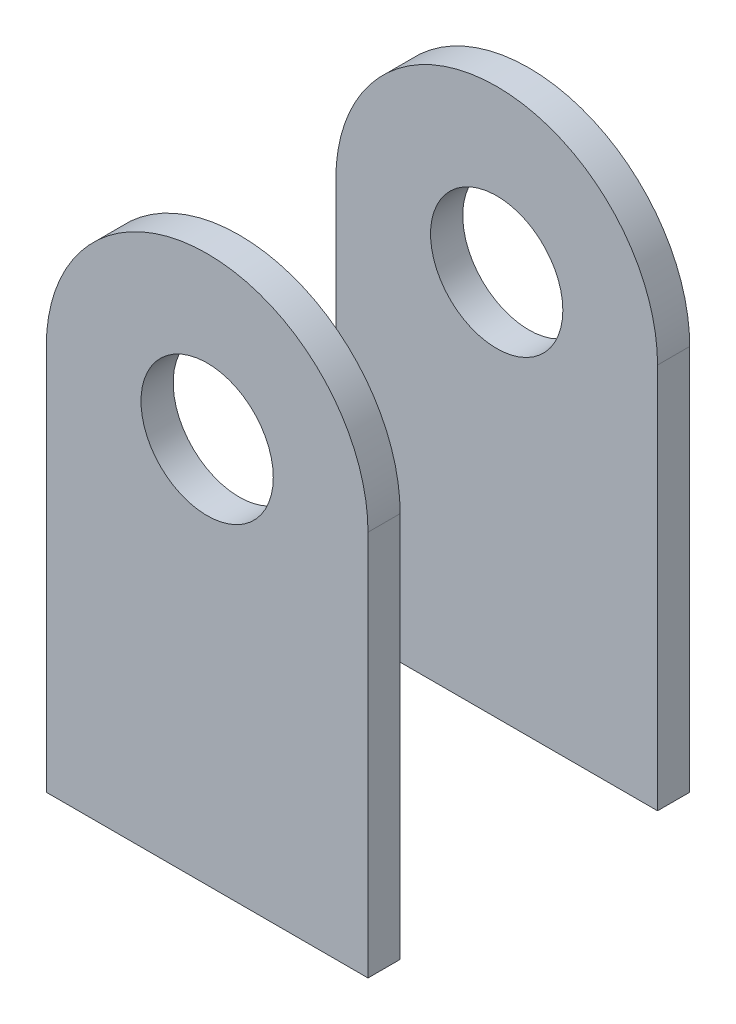
SolidWorks part; units mm, degrees
ref_plane "Front Plane" through (0, 0, 0) normal (0, 0, 1) x (1, 0, 0)
ref_plane "Top Plane" through (0, 0, 0) normal (0, 1, 0) x (1, 0, 0)
ref_plane "Right Plane" through (0, 0, 0) normal (1, 0, 0) x (0, 0, -1)
sketch "Sketch1" plane through (0, 0, 0) normal (0, 0, 1) x (1, 0, 0)
  line L0 (7.9375, 0) -> (7.9375, -19.05)
  line L1 (7.9375, -19.05) -> (-7.9375, -19.05)
  line L2 (-7.9375, -19.05) -> (-7.9375, 0)
  line L3 (0, 0) -> (0, -19.05) construction
  circle A0 centre (0, 0) radius 3.2639
  circle A1 centre (0, 0) radius 7.9375
  dimension "D1" = 6.5278
  dimension "D2" = 15.875
  dimension "D3" = 19.05
extrude "Boss-Extrude1" add sketch "Sketch1" along normal blind 1.5875 from offset 6.35 contours A1 A0 | A1 L2 L1 L0 | L3 A1 L2 L1 region at (5.4539, -5.4539, 0) region at (4.2606, -12.5196, 0) region at (-4.2606, -12.5196, 0)
extrude "Boss-Extrude2" add sketch "Sketch1<4>" against normal blind 1.5875 from offset 6.35 separate body contours A1 A0 | A1 L2 L1 L0 | L3 A1 L2 L1 region at (5.4539, -5.4539, 0) region at (4.2606, -12.5196, 0) region at (-4.2606, -12.5196, 0) offset against normal yes
sketch "Sketch1<4>" plane through (0, 0, 0) normal (0, 0, 1) x (1, 0, 0) same geometry as "Sketch1"
equation "\"Width Between Tabs\"= .5"
equation "\"Tab Thickness\"= 1 / 16"
equation "\"D19@Boss-Extrude1\"=\"Width Between Tabs\"/2"
equation "\"D1@Boss-Extrude1\"=\"Tab Thickness\""
equation "\"D19@Boss-Extrude2\"=\"Width Between Tabs\"/2"
equation "\"D1@Boss-Extrude2\"=\"Tab Thickness\""
